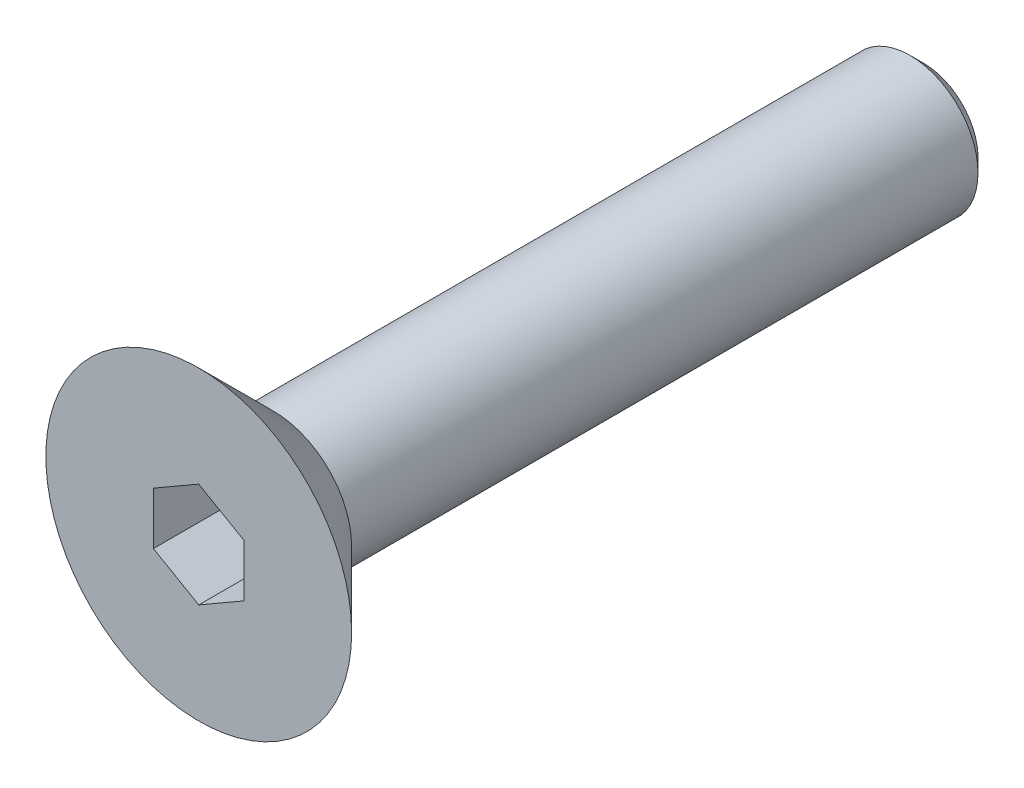
SolidWorks part; units mm, degrees
ref_plane "Front Plane" through (0, 0, 0) normal (0, 0, 1) x (1, 0, 0)
ref_plane "Top Plane" through (0, 0, 0) normal (0, 1, 0) x (1, 0, 0)
ref_plane "Right Plane" through (0, 0, 0) normal (1, 0, 0) x (0, 0, -1)
sketch "Sketch1" plane through (0, 0, 0) normal (0, 0, 1) x (1, 0, 0)
  circle A0 centre (0, 0) radius 3.375
  dimension "D1" = 6.75
extrude "Boss-Extrude1" add sketch "Sketch1" along normal blind 1.65
sketch "Sketch2" plane through (0, 0, 0) normal (0, 0, -1) x (-1, 0, 0)
  circle A0 centre (0, 0) radius 1.5
  dimension "D1" = 3
extrude "Boss-Extrude2" add sketch "Sketch2" along normal blind 14.35
chamfer "Chamfer1" distance 0.3 angle 45 1 edges at (-1.5, 0, -14.35)
sketch "Sketch3" plane through (0, 0, 1.65) normal (0, 0, 1) x (1, 0, 0)
  line L1 (0, 1.1547) -> (-1, 0.5774)
  line L2 (-1, 0.5774) -> (-1, -0.5774)
  line L3 (-1, -0.5774) -> (0, -1.1547)
  line L4 (0, -1.1547) -> (1, -0.5774)
  line L5 (1, -0.5774) -> (1, 0.5774)
  line L6 (1, 0.5774) -> (0, 1.1547)
  circle A0 centre (0, 0) radius 1 construction
  dimension "D1" = 2
extrude "Cut-Extrude1" cut sketch "Sketch3" against normal blind 2
chamfer "Chamfer2" distance 1.65 angle 45 1 edges at (3.375, 0, 0)
